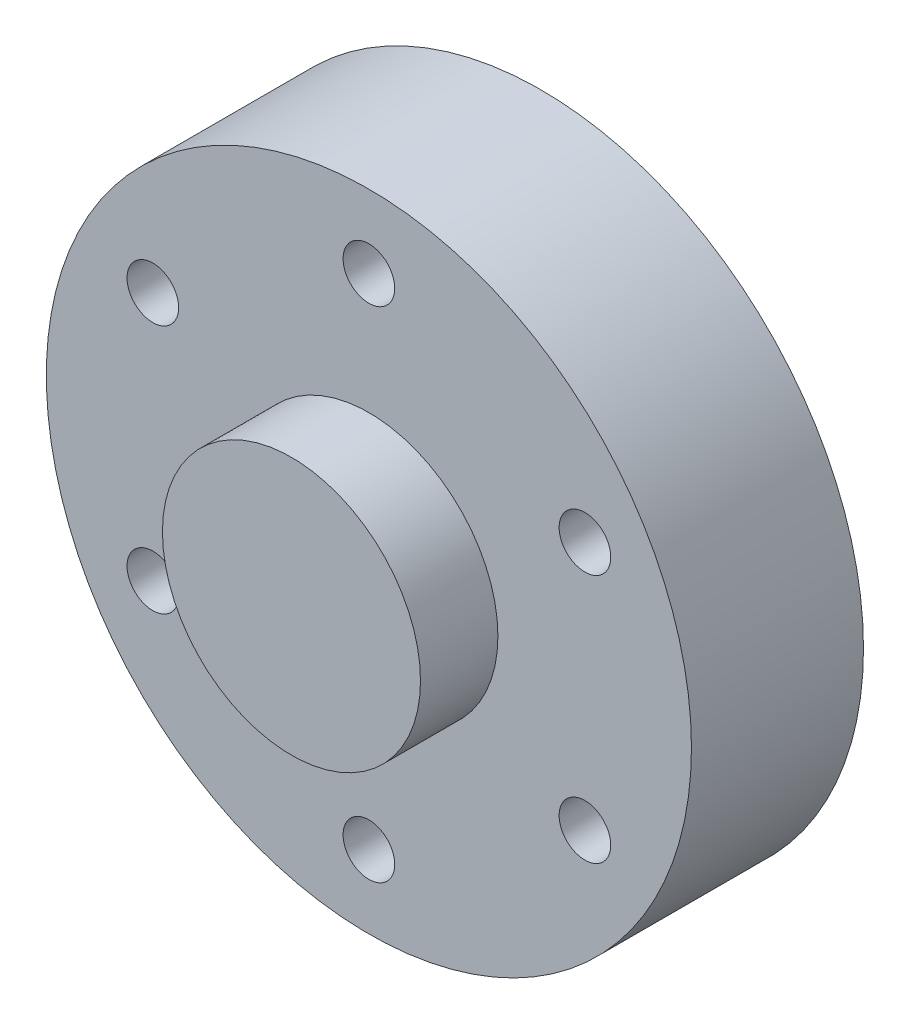
SolidWorks part; units mm, degrees
ref_plane "Front Plane" through (0, 0, 0) normal (0, 0, 1) x (1, 0, 0)
ref_plane "Top Plane" through (0, 0, 0) normal (0, 1, 0) x (1, 0, 0)
ref_plane "Right Plane" through (0, 0, 0) normal (1, 0, 0) x (0, 0, -1)
sketch "Sketch2" plane through (0, 0, 0) normal (0, 0, 1) x (1, 0, 0)
  circle A0 centre (0, 0) radius 9.5
  circle A1 centre (0, 0) radius 14.5 construction
  circle A3 centre (0, 0) radius 18.75
  circle A4 centre (0, 14.5) radius 1.5
  circle A5 centre (12.5574, 7.25) radius 1.5
  circle A6 centre (12.5574, -7.25) radius 1.5
  circle A7 centre (0, -14.5) radius 1.5
  circle A8 centre (-12.5574, -7.25) radius 1.5
  circle A9 centre (-12.5574, 7.25) radius 1.5
  point P21 (0, 0)
  dimension "D1" = 19
  dimension "D3" = 29
  dimension "D4" = 37.5
  dimension "D5" = 3
  dimension "D6" = 6
extrude "Boss-Extrude1" add sketch "Sketch2" along normal blind 10 contours A3 A9 A8 A7 A6 A5 A4 A0 | A0 region at (0, 0, 0) region at (-18.2197, 0, 0)
sketch "Sketch3" plane through (0, 0, 10) normal (0, 0, 1) x (1, 0, 0)
  circle A0 centre (0, 0) radius 7.5
  dimension "D1" = 15
extrude "Boss-Extrude2" add sketch "Sketch3" along normal blind 4.5
sketch "Sketch6" plane through (0, 0, 0) normal (0, 0, -1) x (-1, 0, 0)
  circle A0 centre (0, 0) radius 7.5
  dimension "D1" = 15
extrude "Boss-Extrude4" add sketch "Sketch6" along normal blind 4.5 contours A0
sketch "Sketch7" plane through (0, 0, -4.5) normal (0, 0, -1) x (-1, 0, 0)
  circle A0 centre (0, 0) radius 2
  dimension "D1" = 4
extrude "Boss-Extrude5" add sketch "Sketch7" along normal blind 1
fillet "Fillet2" radius 0.05 1 edges at (-2, 0, -5.5)
sketch "Sketch9" plane through (0, 0, -5.5) normal (0, 0, -1) x (-1, 0, 0)
  circle A0 centre (0, 0) radius 1.7
  dimension "D1" = 3.4
extrude "Cut-Extrude1" cut sketch "Sketch9" against normal blind 13
sketch "Sketch10" plane through (0, 0, -4.5) normal (0, 0, -1) x (-1, 0, 0)
  circle A0 centre (0, 4.5) radius 0.8
  circle A1 centre (0, -4.5) radius 0.8
  dimension "D3" = 1.6
  dimension "D4" = 1.6
  dimension "D1" = 4.5
  dimension "D2" = 4.5
extrude "Cut-Extrude2" cut sketch "Sketch10" against normal blind 5
